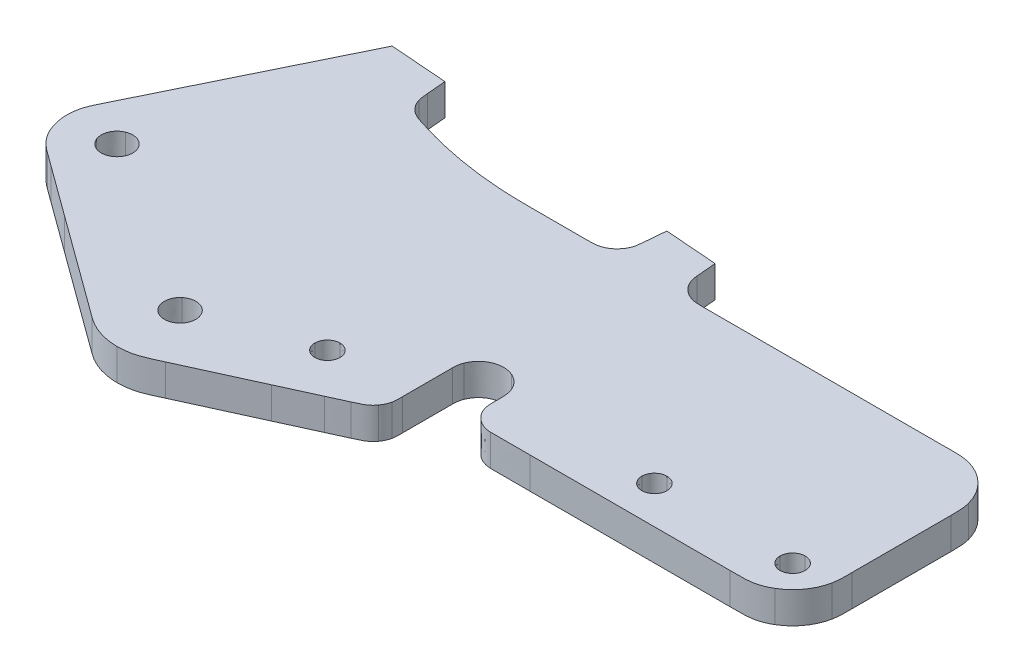
SolidWorks part; units mm, degrees
ref_plane "Front Plane" through (0, 0, 0) normal (0, 0, 1) x (1, 0, 0)
ref_plane "Top Plane" through (0, 0, 0) normal (0, 1, 0) x (1, 0, 0)
ref_plane "Right Plane" through (0, 0, 0) normal (1, 0, 0) x (0, 0, -1)
sketch "Sketch1" plane through (0, 0, 0) normal (0, 1, 0) x (1, 0, 0)
  line L0 (26.2542, 100.7033) -> (40.6892, 99.5939)
  line L1 (101.4193, 94.9221) -> (114.6416, 93.9093)
  line L2 (47.6413, 3.4801) -> (47.6414, 3.4827)
  spline S0 degree 3 poles (47.6414, 3.4827) (39.1389, 9.6839) (30.6295, 15.885) (22.127, 22.0862) knots 0 0 0 0 1 1 1 1
  spline S1 degree 3 poles (22.127, 22.0862) (17.8826, 25.1868) (13.6314, 28.2805) (9.387, 31.381) knots 0 0 0 0 1 1 1 1
  spline S2 degree 3 poles (9.387, 31.381) (8.3259, 32.1527) (7.2649, 32.9314) (6.2038, 33.703) knots 0 0 0 0 1 1 1 1
  spline S3 degree 3 poles (6.2038, 33.703) (5.1358, 34.4816) (4.1092, 35.274) (3.241, 36.2938) knots 0 0 0 0 1 1 1 1
  spline S4 degree 3 poles (3.241, 36.2938) (1.5184, 38.3195) (0.478, 40.8275) (0.2644, 43.4803) knots 0 0 0 0 1 1 1 1
  spline S5 degree 3 poles (0.2644, 43.4803) (0.1542, 44.8307) (0.2503, 46.1192) (0.5607, 47.4421) knots 0 0 0 0 1 1 1 1
  spline S6 degree 3 poles (0.5607, 47.4421) (0.8639, 48.7374) (1.4082, 49.9088) (1.987, 51.0939) knots 0 0 0 0 1 1 1 1
  spline S7 degree 3 poles (1.987, 51.0939) (3.1445, 53.4435) (4.2883, 55.793) (5.4458, 58.1494) knots 0 0 0 0 1 1 1 1
  spline S8 degree 3 poles (5.4458, 58.1494) (7.7541, 62.8762) (10.0691, 67.6097) (12.3774, 72.3363) knots 0 0 0 0 1 1 1 1
  spline S9 degree 3 poles (12.3774, 72.3363) (17.0007, 81.7897) (21.624, 91.2499) (26.2542, 100.7033) knots 0 0 0 0 1 1 1 1
  spline S10 degree 3 poles (40.6892, 99.5939) (40.8338, 97.9679) (40.9716, 96.3487) (41.1164, 94.7226) knots 0 0 0 0 1 1 1 1
  spline S11 degree 3 poles (41.1164, 94.7226) (41.1853, 93.9164) (41.2197, 93.1172) (41.454, 92.3317) knots 0 0 0 0 1 1 1 1
  spline S12 degree 3 poles (41.454, 92.3317) (41.6951, 91.498) (42.0741, 90.7883) (42.6184, 90.1131) knots 0 0 0 0 1 1 1 1
  spline S13 degree 3 poles (42.6184, 90.1131) (43.7691, 88.7006) (45.2091, 88.1907) (46.8214, 87.6808) knots 0 0 0 0 1 1 1 1
  spline S14 degree 3 poles (46.8214, 87.6808) (48.3717, 87.1779) (49.9358, 86.7231) (51.5205, 86.3028) knots 0 0 0 0 1 1 1 1
  spline S15 degree 3 poles (51.5205, 86.3028) (57.9078, 84.6009) (64.3087, 83.5467) (70.9027, 83.1058) knots 0 0 0 0 1 1 1 1
  spline S16 degree 3 poles (70.9027, 83.1058) (74.1824, 82.8853) (77.4552, 82.8782) (80.7349, 82.8782) knots 0 0 0 0 1 1 1 1
  spline S17 degree 3 poles (80.7349, 82.8782) (84.0147, 82.8782) (87.2944, 82.8782) (90.5742, 82.8782) knots 0 0 0 0 1 1 1 1
  spline S18 degree 3 poles (90.5742, 82.8782) (91.146, 82.8782) (94.7841, 82.8583) (95.3559, 82.9332) knots 0 0 0 0 1 1 1 1
  spline S19 degree 3 poles (95.3559, 82.9332) (97.0441, 83.1467) (98.5737, 84.0357) (99.6072, 85.393) knots 0 0 0 0 1 1 1 1
  spline S20 degree 3 poles (99.6072, 85.393) (100.813, 86.9778) (100.8336, 88.1973) (100.9921, 90.037) knots 0 0 0 0 1 1 1 1
  spline S21 degree 3 poles (100.9921, 90.037) (101.1368, 91.67) (101.2815, 93.2961) (101.4193, 94.9221) knots 0 0 0 0 1 1 1 1
  spline S22 degree 3 poles (114.6416, 93.9093) (114.7863, 92.235) (114.931, 90.5675) (115.0757, 88.8932) knots 0 0 0 0 1 1 1 1
  spline S23 degree 3 poles (115.0757, 88.8932) (115.248, 86.9985) (115.8336, 85.6411) (117.3081, 84.3939) knots 0 0 0 0 1 1 1 1
  spline S24 degree 3 poles (117.3081, 84.3939) (118.7688, 83.1537) (120.2571, 82.8781) (122.0761, 82.8781) knots 0 0 0 0 1 1 1 1
  spline S25 degree 3 poles (122.0761, 82.8781) (123.7573, 82.8781) (125.4316, 82.8781) (127.1128, 82.8781) knots 0 0 0 0 1 1 1 1
  spline S26 degree 3 poles (127.1128, 82.8781) (133.8307, 82.8781) (140.5487, 82.8781) (147.2666, 82.8781) knots 0 0 0 0 1 1 1 1
  spline S27 degree 3 poles (147.2666, 82.8781) (154.019, 82.8781) (160.7783, 82.8781) (167.5307, 82.8781) knots 0 0 0 0 1 1 1 1
  spline S28 degree 3 poles (167.5307, 82.8781) (170.9069, 82.8781) (174.2831, 82.8781) (177.6662, 82.8781) knots 0 0 0 0 1 1 1 1
  spline S29 degree 3 poles (177.6662, 82.8781) (179.3543, 82.8781) (181.0424, 82.8781) (182.7304, 82.8781) knots 0 0 0 0 1 1 1 1
  spline S30 degree 3 poles (182.7304, 82.8781) (184.3979, 82.8781) (186.0653, 82.9677) (187.7327, 82.8431) knots 0 0 0 0 1 1 1 1
  spline S31 degree 3 poles (187.7327, 82.8431) (191.2467, 82.5882) (194.492, 80.8932) (196.7106, 78.1509) knots 0 0 0 0 1 1 1 1
  spline S32 degree 3 poles (196.7106, 78.1509) (197.8475, 76.7385) (198.6054, 75.2571) (199.0809, 73.5069) knots 0 0 0 0 1 1 1 1
  spline S33 degree 3 poles (199.0809, 73.5069) (199.5218, 71.8877) (199.5218, 70.2892) (199.5218, 68.6493) knots 0 0 0 0 1 1 1 1
  spline S34 degree 3 poles (199.5218, 68.6493) (199.5218, 61.9934) (199.5218, 55.3237) (199.5218, 48.6609) knots 0 0 0 0 1 1 1 1
  spline S35 degree 3 poles (199.5218, 48.6609) (199.5218, 46.9935) (199.5218, 45.326) (199.5218, 43.6655) knots 0 0 0 0 1 1 1 1
  spline S36 degree 3 poles (199.5218, 43.6655) (199.5218, 42.0325) (199.5977, 40.4202) (199.2669, 38.7941) knots 0 0 0 0 1 1 1 1
  spline S37 degree 3 poles (199.2669, 38.7941) (198.5434, 35.2871) (196.3799, 32.2484) (193.3, 30.4225) knots 0 0 0 0 1 1 1 1
  spline S38 degree 3 poles (193.3, 30.4225) (189.8273, 28.3693) (187.3193, 28.6449) (183.5986, 28.6449) knots 0 0 0 0 1 1 1 1
  spline S39 degree 3 poles (183.5986, 28.6449) (180.2706, 28.6449) (176.9357, 28.6449) (173.6078, 28.6449) knots 0 0 0 0 1 1 1 1
  spline S40 degree 3 poles (173.6078, 28.6449) (160.0961, 28.6449) (146.5845, 28.6449) (133.0728, 28.6449) knots 0 0 0 0 1 1 1 1
  spline S41 degree 3 poles (133.0728, 28.6449) (129.7724, 28.6449) (126.472, 28.5689) (123.1647, 28.6499) knots 0 0 0 0 1 1 1 1
  spline S42 degree 3 poles (123.1647, 28.6499) (121.4353, 28.6899) (119.8023, 29.4354) (118.631, 30.7169) knots 0 0 0 0 1 1 1 1
  spline S43 degree 3 poles (118.631, 30.7169) (117.3632, 32.1156) (116.9773, 33.535) (116.9773, 35.3609) knots 0 0 0 0 1 1 1 1
  spline S44 degree 3 poles (116.9773, 35.3609) (116.9773, 36.739) (117.1013, 38.8543) (116.6121, 40.2392) knots 0 0 0 0 1 1 1 1
  spline S45 degree 3 poles (116.6121, 40.2392) (116.0196, 41.9273) (114.7449, 43.2846) (113.0981, 43.9805) knots 0 0 0 0 1 1 1 1
  spline S46 degree 3 poles (113.0981, 43.9805) (109.7839, 45.3792) (105.9943, 43.767) (104.699, 40.4115) knots 0 0 0 0 1 1 1 1
  spline S47 degree 3 poles (104.699, 40.4115) (104.3889, 39.6122) (104.2718, 38.8198) (104.2718, 37.9723) knots 0 0 0 0 1 1 1 1
  spline S48 degree 3 poles (104.2718, 37.9723) (104.2718, 37.1248) (104.2718, 36.2842) (104.2718, 35.4436) knots 0 0 0 0 1 1 1 1
  spline S49 degree 3 poles (104.2718, 35.4436) (104.2718, 33.7555) (104.2718, 32.0674) (104.2718, 30.3793) knots 0 0 0 0 1 1 1 1
  spline S50 degree 3 poles (104.2718, 30.3793) (104.2718, 28.6912) (104.2718, 27.0031) (104.2718, 25.315) knots 0 0 0 0 1 1 1 1
  spline S51 degree 3 poles (104.2718, 25.315) (104.2718, 24.4813) (104.3133, 23.6545) (104.134, 22.8139) knots 0 0 0 0 1 1 1 1
  spline S52 degree 3 poles (104.134, 22.8139) (103.9411, 21.9319) (103.6035, 21.174) (103.0798, 20.4436) knots 0 0 0 0 1 1 1 1
  spline S53 degree 3 poles (103.0798, 20.4436) (101.9843, 18.9209) (100.4891, 18.3422) (98.9181, 17.6256) knots 0 0 0 0 1 1 1 1
  spline S54 degree 3 poles (98.9181, 17.6256) (97.3885, 16.9297) (95.852, 16.2269) (94.3155, 15.531) knots 0 0 0 0 1 1 1 1
  spline S55 degree 3 poles (94.3155, 15.531) (91.2425, 14.1253) (88.1694, 12.7266) (85.1033, 11.3279) knots 0 0 0 0 1 1 1 1
  spline S56 degree 3 poles (85.1033, 11.3279) (78.9917, 8.5443) (72.8801, 5.7607) (66.7754, 2.977) knots 0 0 0 0 1 1 1 1
  spline S57 degree 3 poles (66.7754, 2.977) (63.3027, 1.3992) (61.1875, 0.1934) (57.1567, 0.221) knots 0 0 0 0 1 1 1 1
  spline S58 degree 3 poles (57.1567, 0.221) (53.7185, 0.251) (50.3767, 1.3923) (47.6413, 3.4801) knots 0 0 0 0 1 1 1 1
  spline S59 degree 3 poles (193.176, 38.1335) (193.176, 39.8835) (191.7566, 41.3098) (189.9996, 41.3098) knots 0 0 0 0 1 1 1 1
  spline S60 degree 3 poles (189.9996, 41.3098) (188.2495, 41.3098) (186.8232, 39.8835) (186.8232, 38.1335) knots 0 0 0 0 1 1 1 1
  spline S61 degree 3 poles (186.8232, 38.1335) (186.8232, 36.3764) (188.2495, 34.9571) (189.9996, 34.9571) knots 0 0 0 0 1 1 1 1
  spline S62 degree 3 poles (189.9996, 34.9571) (191.7566, 34.9571) (193.176, 36.3764) (193.176, 38.1335) knots 0 0 0 0 1 1 1 1
  spline S63 degree 3 poles (60.3193, 18.648) (58.9137, 20.3292) (56.4057, 20.5497) (54.7314, 19.137) knots 0 0 0 0 1 1 1 1
  spline S64 degree 3 poles (54.7314, 19.137) (53.0502, 17.7314) (52.8297, 15.2234) (54.2353, 13.549) knots 0 0 0 0 1 1 1 1
  spline S65 degree 3 poles (54.2353, 13.549) (55.6478, 11.8678) (58.1558, 11.6542) (59.8301, 13.06) knots 0 0 0 0 1 1 1 1
  spline S66 degree 3 poles (59.8301, 13.06) (61.5113, 14.4656) (61.7249, 16.9737) (60.3193, 18.648) knots 0 0 0 0 1 1 1 1
  spline S67 degree 3 poles (87.8043, 25.9654) (87.8043, 27.7155) (86.3849, 29.1349) (84.6348, 29.1349) knots 0 0 0 0 1 1 1 1
  spline S68 degree 3 poles (84.6348, 29.1349) (82.8778, 29.1349) (81.4584, 27.7155) (81.4584, 25.9654) knots 0 0 0 0 1 1 1 1
  spline S69 degree 3 poles (81.4584, 25.9654) (81.4584, 24.2084) (82.8778, 22.789) (84.6348, 22.789) knots 0 0 0 0 1 1 1 1
  spline S70 degree 3 poles (84.6348, 22.789) (86.3849, 22.789) (87.8043, 24.2084) (87.8043, 25.9654) knots 0 0 0 0 1 1 1 1
  spline S71 degree 3 poles (158.2496, 38.1335) (158.2496, 39.8835) (156.8302, 41.3098) (155.0732, 41.3098) knots 0 0 0 0 1 1 1 1
  spline S72 degree 3 poles (155.0732, 41.3098) (153.3231, 41.3098) (151.8969, 39.8835) (151.8969, 38.1335) knots 0 0 0 0 1 1 1 1
  spline S73 degree 3 poles (151.8969, 38.1335) (151.8969, 36.3764) (153.3231, 34.9571) (155.0732, 34.9571) knots 0 0 0 0 1 1 1 1
  spline S74 degree 3 poles (155.0732, 34.9571) (156.8302, 34.9571) (158.2496, 36.3764) (158.2496, 38.1335) knots 0 0 0 0 1 1 1 1
  spline S75 degree 3 poles (16.5804, 46.0434) (15.7398, 48.0622) (13.4178, 49.0269) (11.399, 48.1862) knots 0 0 0 0 1 1 1 1
  spline S76 degree 3 poles (11.399, 48.1862) (9.3732, 47.3525) (8.4086, 45.0305) (9.2492, 43.0048) knots 0 0 0 0 1 1 1 1
  spline S77 degree 3 poles (9.2492, 43.0048) (10.0898, 40.9791) (12.4118, 40.0144) (14.4307, 40.8551) knots 0 0 0 0 1 1 1 1
  spline S78 degree 3 poles (14.4307, 40.8551) (16.4564, 41.6957) (17.421, 44.0177) (16.5804, 46.0434) knots 0 0 0 0 1 1 1 1
extrude "Boss-Extrude1" add sketch "Sketch1" along normal blind 7.9375
sketch "Sketch2" plane through (7.8204, 0, -102.092) normal (0.0764, 0, -0.9971) x (-0.9971, 0, -0.0764)
  line L0 (-100.5036, 3.9688) -> (-26.3356, 3.9688) construction
  line L1 (-93.8731, 7.9375) -> (-107.1341, 7.9375) construction
  line L2 (-93.8731, 7.9375) -> (-93.8731, 0) construction
  line L3 (-93.8731, 0) -> (-107.1341, 0) construction
  line L4 (-107.1341, 7.9375) -> (-107.1341, 0) construction
  line L5 (-93.8731, 7.9375) -> (-107.1341, 0) construction
  line L6 (-93.8731, 0) -> (-107.1341, 7.9375) construction
  point P4 (-100.5036, 3.9688)
  dimension "D1" = 74.168
sketch "Sketch5" plane through (7.8481, 0, -102.1179) normal (0.0766, 0, -0.9971) x (-0.9971, 0, -0.0766)
  point P0 (-26.31, 3.9688)
hole_wizard "M6x1.0 Tapped Hole5" positions "3DSketch2" profile "Sketch4" tap size "M6x1.0" standard "ANSI Metric"
sketch3d "3DSketch2"
  point P0 (108.0305, 3.9688, -94.4157)
  point P3 (34.0808, 3.9688, -100.1018)
sketch "Sketch4" plane through (108.0305, 3.9688, -94.4157) normal (0, 1, 0) x (-0.9971, 0, -0.0764)
  line L0 (0, 0) -> (0, 13.5022)
  line L1 (0, 13.5022) -> (2.5, 12)
  line L2 (2.5, 12) -> (2.5, 0.525)
  line L3 (2.5, 0.525) -> (3.025, 0)
  line L5 (3.025, 0) -> (0, 0)
  line L6 (-2.5, 0.525) -> (-3.025, 0) construction
  line L10 (0, 13.5022) -> (-2.5, 12) construction
  line L11 (0, -6.35) -> (0, 107.95) construction
  dimension "Tap Drill Dia." = 5
  dimension "Tap Drill Depth" = 12
  dimension "Near C'Sink Dia." = 6.05
  dimension "Near C'Sink Angle" = 90
  dimension "Drill Angle" = 118
cosmetic thread "Hole Thread2" parameters "D1"=11.938, "D2"=6
cosmetic thread "Hole Thread3" parameters "D1"=11.938, "D2"=6
